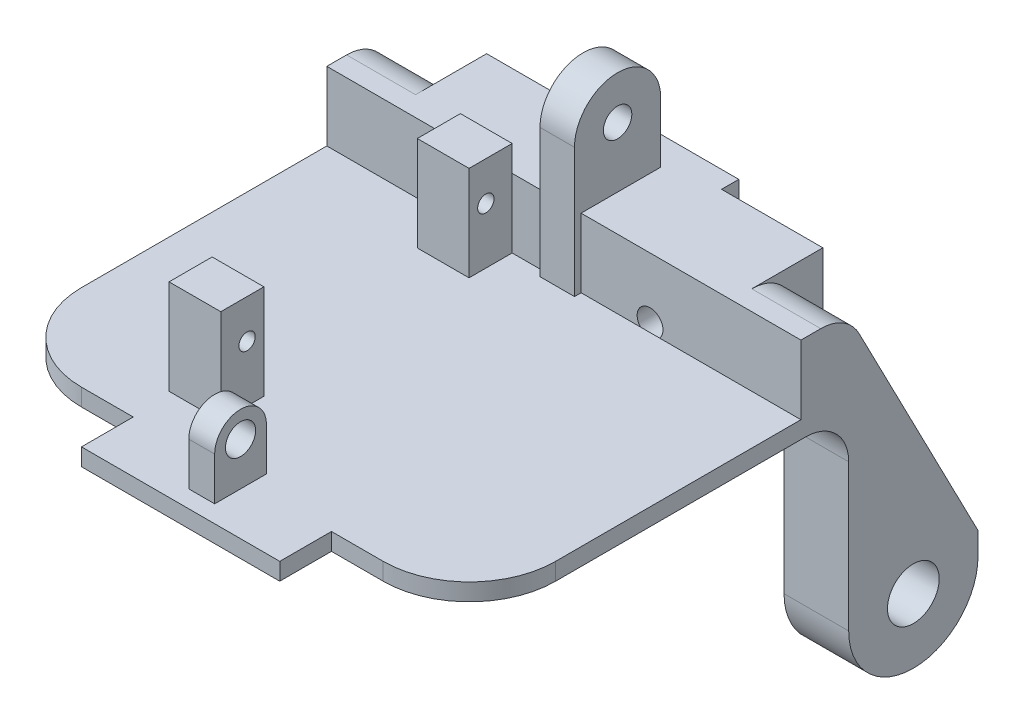
SolidWorks part; units mm, degrees
ref_plane "前视基准面" through (0, 0, 0) normal (0, 0, 1) x (1, 0, 0)
ref_plane "上视基准面" through (0, 0, 0) normal (0, 1, 0) x (1, 0, 0)
ref_plane "右视基准面" through (0, 0, 0) normal (1, 0, 0) x (0, 0, -1)
sketch "草图1" plane through (0, 0, 0) normal (0, 1, 0) x (1, 0, 0)
  line L1 (-27.5, -19.5) -> (27.5, -19.5)
  line L2 (-27.5, -19.5) -> (-27.5, 19.5)
  line L3 (-27.5, 19.5) -> (27.5, 19.5)
  line L4 (27.5, -19.5) -> (27.5, 19.5)
  line L5 (-27.5, -19.5) -> (27.5, 19.5) construction
  line L6 (-27.5, 19.5) -> (27.5, -19.5) construction
  point P0 (0, 0)
  dimension "D1" = 55
  dimension "D2" = 39
extrude "凸台-拉伸1" add sketch "草图1" along normal blind 2
sketch "草图2" plane through (0, 2, 0) normal (0, 1, 0) x (1, 0, 0)
  line L0 (-27.5, -19.5) -> (27.5, -19.5) construction
  line L1 (-11.5, -19.5) -> (11.5, -19.5)
  line L2 (-11.5, -19.5) -> (-11.5, -25.5)
  line L3 (-11.5, -25.5) -> (11.5, -25.5)
  line L4 (11.5, -19.5) -> (11.5, -25.5)
  line L5 (27.5, 19.5) -> (-27.5, 19.5) construction
  point P9 (0, -25.5)
  dimension "D1" = 23
  dimension "D2" = 45
extrude "凸台-拉伸2" add sketch "草图2" against normal blind 2
sketch "草图3" plane through (0, 2, 0) normal (0, 1, 0) x (1, 0, 0)
  line L1 (-6, -14.8415) -> (-12, -14.8415)
  line L2 (-6, -14.8415) -> (-6, -9.8415)
  line L3 (-6, -9.8415) -> (-12, -9.8415)
  line L4 (-12, -14.8415) -> (-12, -9.8415)
  line L6 (-6, 13.9585) -> (-12, 13.9585)
  line L7 (-6, 13.9585) -> (-6, 18.9585)
  line L8 (-6, 18.9585) -> (-12, 18.9585)
  line L9 (-12, 13.9585) -> (-12, 18.9585)
  dimension "D1" = 6
  dimension "D2" = 23.8
  dimension "D3" = 6
  dimension "D4" = 6
  dimension "D5" = 6
  dimension "D6" = 5
  dimension "D7" = 5
extrude "凸台-拉伸3" add sketch "草图3" along normal blind 11
sketch "草图5" plane through (-12, 0, 0) normal (-1, 0, 0) x (0, 0, 1)
  line L0 (-13.9585, 13) -> (-13.9585, 2) construction
  line L1 (9.8415, 13) -> (9.8415, 2) construction
  line L2 (-19.5, 2) -> (19.5, 2) construction
  line L3 (9.8415, 2) -> (14.8415, 2) construction
  circle A0 centre (-15.9085, 8.5) radius 0.95
  circle A1 centre (11.7915, 8.5) radius 0.95
  dimension "D1" = 1.95
  dimension "D2" = 1.95
  dimension "D3" = 6.5
  dimension "D4" = 6.5
  dimension "D5" = 27.7
  dimension "D6" = 1.9
  dimension "D7" = 1.9
extrude "切除-拉伸1" cut sketch "草图5" against normal blind 11
sketch "草图6" plane through (0, 2, 0) normal (0, 1, 0) x (1, 0, 0)
  line L0 (27.5, -19.5) -> (27.5, 19.5) construction
  line L1 (-27.5, 19.5) -> (27.5, 19.5)
  line L2 (-27.5, 19.5) -> (-27.5, 18.9585)
  line L3 (-27.5, 18.9585) -> (27.5, 18.9585)
  line L4 (27.5, 19.5) -> (27.5, 18.9585)
  line L5 (-6, 18.9585) -> (-12, 18.9585) construction
extrude "凸台-拉伸4" add sketch "草图6" along normal blind 8
sketch "草图8" plane through (0, 0, 0) normal (1, 0, 0) x (0, 0, -1)
  line L0 (28.1899, 17) -> (28.1899, 0)
  line L1 (-19.5, 2) -> (18.9585, 2) construction
  line L2 (18.1899, 17) -> (18.1899, 0)
  line L4 (18.1899, 0) -> (28.1899, 0)
  line L7 (-19.5, 0) -> (19.5, 0) construction
  arc A0 (28.1899, 17) -> (18.1899, 17) centre (23.1899, 17) ccw
  circle A1 centre (23.1899, 17) radius 1.65
  dimension "D1" = 15
  dimension "D2" = 10
  dimension "D3" = 3.3
extrude "凸台-拉伸6" add sketch "草图8" along normal mid plane 4
sketch "草图10" plane through (0, 2, 0) normal (0, 1, 0) x (1, 0, 0)
  line L0 (-11.5, -25.5) -> (11.5, -25.5) construction
  line L1 (-1.05, -17.5) -> (1.95, -17.5)
  line L2 (-1.05, -17.5) -> (-1.05, -23.5)
  line L3 (-1.05, -23.5) -> (1.95, -23.5)
  line L4 (1.95, -17.5) -> (1.95, -23.5)
  line L7 (11.5, -25.5) -> (11.5, -19.5) construction
  dimension "D1" = 2
  dimension "D2" = 3
  dimension "D3" = 6
  dimension "D4" = 9.55
extrude "凸台-拉伸7" add sketch "草图10" along normal blind 8
sketch "草图11" plane through (0, 0, -18.9585) normal (0, 0, 1) x (1, 0, 0)
  line L0 (-2, 10) -> (-27.5, 10) construction
  circle A0 centre (-10, 3) radius 1.5
  dimension "D1" = 10
  dimension "D2" = 3
  dimension "D3" = 7
extrude "切除-拉伸3" cut sketch "草图11" against normal blind 13
sketch "草图12" plane through (-27.5, 0, 0) normal (-1, 0, 0) x (0, 0, 1)
  line L1 (-19.5, 0) -> (4.0888, 0)
  line L2 (-19.5, 0) -> (19.5, 0) construction
  line L3 (-19.5, 10) -> (-19.5, 0) construction
  line L4 (-39.5, -22) -> (-39.5, 10)
  line L5 (-19.5, 10) -> (-39.5, 10)
  line L6 (-24.5, -22) -> (-24.5, 0)
  line L7 (-24.5, 0) -> (-19.5, 0)
  line L8 (-19.5, 10) -> (-19.5, 0)
  arc A0 (-39.5, -22) -> (-24.5, -22) centre (-32, -22) ccw
  circle A2 centre (-32, -22) radius 3
  line M7 (-19.5, 10) -> (-19.5, 0)
  dimension "D1" = 15
  dimension "D5" = 6
  dimension "D2" = 22
  dimension "D3" = 12.5
extrude "凸台-拉伸8" add sketch "草图12" against normal blind 7.5 contours L4 A0 L6 L7 L5 A2 M7 region at (-27.5, -7.1737, -31.1527)
sketch "草图13" plane through (0, 0, 0) normal (0, -1, 0) x (1, 0, 0)
  line L0 (-11.5, 25.5) -> (11.5, 25.5) construction
  line L1 (-5, 20) -> (5, 20)
  line L2 (-5, 20) -> (-5, 16.3)
  line L3 (-5, 16.3) -> (5, 16.3)
  line L4 (5, 20) -> (5, 16.3)
  line L5 (-5, 20) -> (5, 16.3) construction
  line L6 (-5, 16.3) -> (5, 20) construction
  point P0 (0, 18.15)
  dimension "D1" = 10
  dimension "D2" = 5.5
  dimension "D3" = 3.7
extrude "凸台-拉伸9" add sketch "草图13" along normal blind 1
mirror "镜向1" about plane through (0, 0, 0) normal (1, 0, 0) of "凸台-拉伸8", "切除-拉伸3"
fillet "圆角3" 2 edges at (0.45, 10, 17.5) (0.45, 10, 23.5) type full round first side face at (0.45, 6, 17.5) second side face at (0.45, 6, 23.5) middle face at (0.45, 10, 20.5)
sketch "草图15" plane through (-1.05, 0, 0) normal (-1, 0, 0) x (0, 0, 1)
  circle A0 centre (20.5, 7) radius 1.75
  dimension "D1" = 3.5
extrude "切除-拉伸5" cut sketch "草图15" against normal blind 23
sketch "草图16" plane through (0, 0, -19.5) normal (0, 0, -1) x (-1, 0, 0)
  line L0 (-20, 10) -> (-2, 10) construction
  line L1 (-7.75, 10) -> (7.75, 10)
  line L2 (-7.75, 10) -> (-7.75, 6)
  line L3 (-7.75, 6) -> (7.75, 6)
  line L4 (7.75, 10) -> (7.75, 6)
  point P6 (0, 6)
  dimension "D1" = 15.5
  dimension "D2" = 4
extrude "凸台-拉伸10" add sketch "草图16" along normal blind 20
sketch "草图17" plane through (0, 0, -19.5) normal (0, 0, -1) x (-1, 0, 0)
  line L6 (-20, 0) -> (-2, 0)
  line L7 (-20, 0) -> (-2, 0)
  line L8 (-20, 10) -> (-20, 0)
  line L10 (-7.75, 6) -> (-7.75, 10)
  line L11 (-7.75, 10) -> (-20, 10)
  line L12 (-2, 0) -> (-2, 6)
  line L14 (-2, 0) -> (-2, 6)
  line L15 (-7.75, 6) -> (-7.75, 10)
  line L16 (-2, 6) -> (-7.75, 6)
  line L18 (-2, 6) -> (-7.75, 6)
  line L21 (-7.75, 10) -> (-20, 10)
  line L32 (-20, 10) -> (-20, 0)
  line L33 (7.75, 6) -> (2, 6)
  line L34 (2, 6) -> (2, 0)
  line L35 (2, 0) -> (20, 0)
  line L36 (20, 0) -> (20, 10)
  line L37 (20, 10) -> (7.75, 10)
  line L38 (7.75, 10) -> (7.75, 6)
  line L39 (7.75, 6) -> (2, 6)
  line L40 (2, 6) -> (2, 0)
  line L41 (2, 0) -> (20, 0)
  line L42 (20, 0) -> (20, 10)
  line L43 (20, 10) -> (7.75, 10)
  line L44 (7.75, 10) -> (7.75, 6)
  circle A0 centre (10, 3) radius 1.5 construction
  circle A1 centre (-10, 3) radius 1.5 construction
  circle A2 centre (10, 3) radius 1.5
  circle A3 centre (-10, 3) radius 1.5
  dimension "D1" = 0
  dimension "D2" = 0
extrude "凸台-拉伸11" add sketch "草图17" along normal blind 10
fillet "圆角4" radius 10 2 edges at (23.75, 10, -39.5) (-23.75, 10, -39.5)
sketch "草图18" plane through (0, 10, 0) normal (0, 1, 0) x (1, 0, 0)
  line L0 (-7.75, 39.5) -> (7.75, 39.5) construction
  line L1 (-14.1233, 41.9545) -> (12.4415, 41.9545)
  line L2 (-14.1233, 41.9545) -> (-14.1233, 31.5)
  line L3 (-14.1233, 31.5) -> (12.4415, 31.5)
  line L4 (12.4415, 41.9545) -> (12.4415, 31.5)
  dimension "D1" = 8
extrude "切除-拉伸6" cut sketch "草图18" against normal blind 10
sketch "草图19" plane through (27.5, 0, 0) normal (1, 0, 0) x (0, 0, -1)
  line L0 (24.3, 10) -> (39.5, -19.3956)
  line L1 (39.5, -22) -> (39.5, 0) construction
  line L2 (24.3, 10) -> (39.5, 10)
  line L3 (39.5, 10) -> (39.5, -19.3956)
  dimension "D1" = 15.2
extrude "切除-拉伸7" cut sketch "草图19" against normal blind 8
sketch "草图20" plane through (-27.5, 0, 0) normal (-1, 0, 0) x (0, 0, 1)
  line L0 (-24.3, 10) -> (-39.5, 10)
  line L1 (-39.5, 10) -> (-39.5, -19.3956)
  line L8 (-39.5, -19.3956) -> (-39.5, -22)
  line L9 (-24.3, 10) -> (-39.5, -19.3956)
  line L10 (-18.9585, 10) -> (-24.3, 10)
  line L11 (-18.9585, 2) -> (-18.9585, 10)
  line L12 (19.5, 2) -> (-18.9585, 2)
  line L13 (19.5, 0) -> (19.5, 2)
  line L14 (-24.5, 0) -> (19.5, 0)
  line L15 (-24.5, -22) -> (-24.5, 0)
  line L17 (-24.3, 10) -> (-39.5, -19.3956)
  arc A1 (-39.5, -22) -> (-24.5, -22) centre (-32, -22) ccw
  dimension "D1" = 0
extrude "切除-拉伸8" cut sketch "草图20" against normal blind 8
fillet "圆角6" radius 5 4 edges at (23.75, 0, -24.5) (-23.75, 0, -24.5) (23.5, 10, -24.3) (-23.5, 10, -24.3)
fillet "圆角7" radius 10 2 edges at (27.5, 1, 19.5) (-27.5, 1, 19.5)
sketch "草图21" plane through (0, -1, 0) normal (0, -1, 0) x (1, 0, 0)
  line L0 (-11.5, 25.5) -> (11.5, 25.5) construction
  line L1 (-27.5, -19.5) -> (-27.5, 9.5) construction
  circle A0 centre (0, 18.15) radius 1.4
  dimension "D1" = 2.8
  dimension "D2" = 7.35
  dimension "D3" = 27.5
extrude "切除-拉伸9" cut sketch "草图21" against normal blind 4
